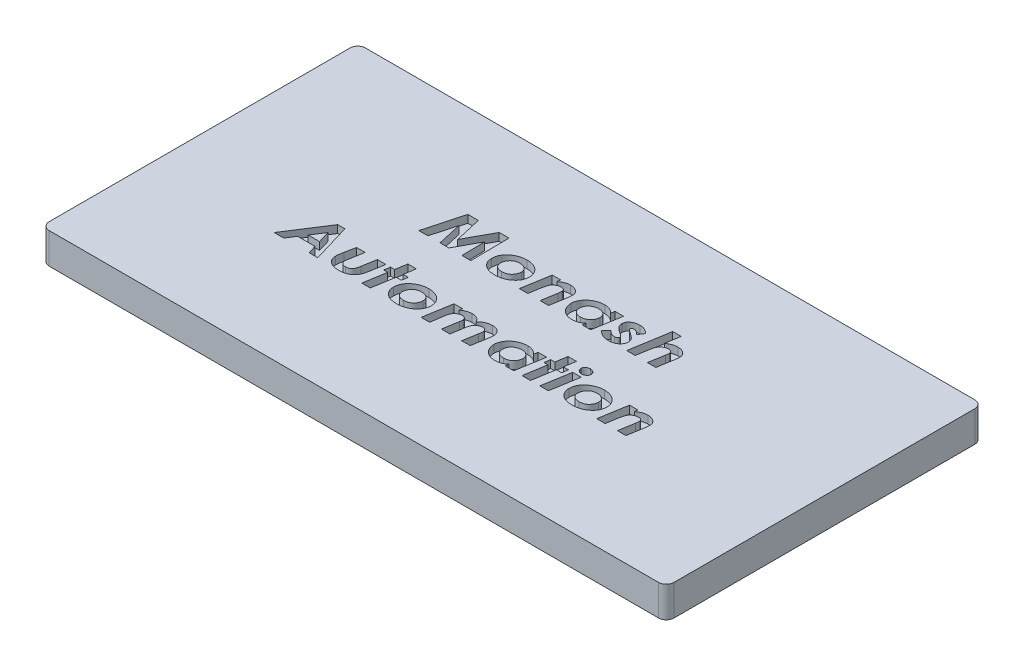
SolidWorks part; units mm, degrees
ref_plane "Front Plane" through (0, 0, 0) normal (0, 0, 1) x (1, 0, 0)
ref_plane "Top Plane" through (0, 0, 0) normal (0, 1, 0) x (1, 0, 0)
ref_plane "Right Plane" through (0, 0, 0) normal (1, 0, 0) x (0, 0, -1)
sketch "Sketch1" plane through (0, 0, 0) normal (0, 1, 0) x (1, 0, 0)
  line L1 (-39.5, 20.5) -> (39.5, 20.5)
  line L2 (-40.5, 19.5) -> (-40.5, -19.5)
  line L3 (-39.5, -20.5) -> (39.5, -20.5)
  line L4 (40.5, 19.5) -> (40.5, -19.5)
  line L5 (-40.5, 20.5) -> (40.5, -20.5) construction
  line L6 (-40.5, -20.5) -> (40.5, 20.5) construction
  line L10 (-20, 0) -> (20, 0) construction
  line L15 (40.5, 20.5) -> (40.5, 23.5)
  circle A0 centre (-20, 0) radius 4.75
  circle A1 centre (20, 0) radius 4.75
  arc A2 (39.5, 20.5) -> (40.5, 19.5) centre (39.5, 19.5) cw
  arc A3 (39.5, -20.5) -> (40.5, -19.5) centre (39.5, -19.5) ccw
  arc A4 (-40.5, -19.5) -> (-39.5, -20.5) centre (-39.5, -19.5) ccw
  arc A5 (-39.5, 20.5) -> (-40.5, 19.5) centre (-39.5, 19.5) ccw
  point P0 (0, 0)
  point P12 (0, 0)
  dimension "D5" = 9.5
  dimension "D3" = 1
  dimension "D1" = 41
  dimension "D2" = 81
  dimension "D4" = 40
extrude "Boss-Extrude4" add sketch "Sketch1" along normal blind 4 contours L4 L1 L2 L3 A1 A0 | A1 | A0 region at (0, 0, 0) region at (-20, 0, 0) region at (20, 0, 0)
extrude "Boss-Extrude5" add sketch "Sketch1<7>" against normal blind 7 contours A1 | A0 region at (-20, 0, 0) region at (20, 0, 0)
sketch "Sketch1<7>" plane through (0, 0, 0) normal (0, 1, 0) x (1, 0, 0) same geometry as "Sketch1"
sketch "Sketch3" plane through (0, 4, 0) normal (0, 1, 0) x (1, 0, 0)
  text T0 "<b><i>    Monash </i></b>\r\n<b><i>Automation</i></b>\r\n" font "Century Gothic" height 5
extrude "Cut-Extrude2" cut sketch "Sketch3" against normal blind 1 and the other way through all
